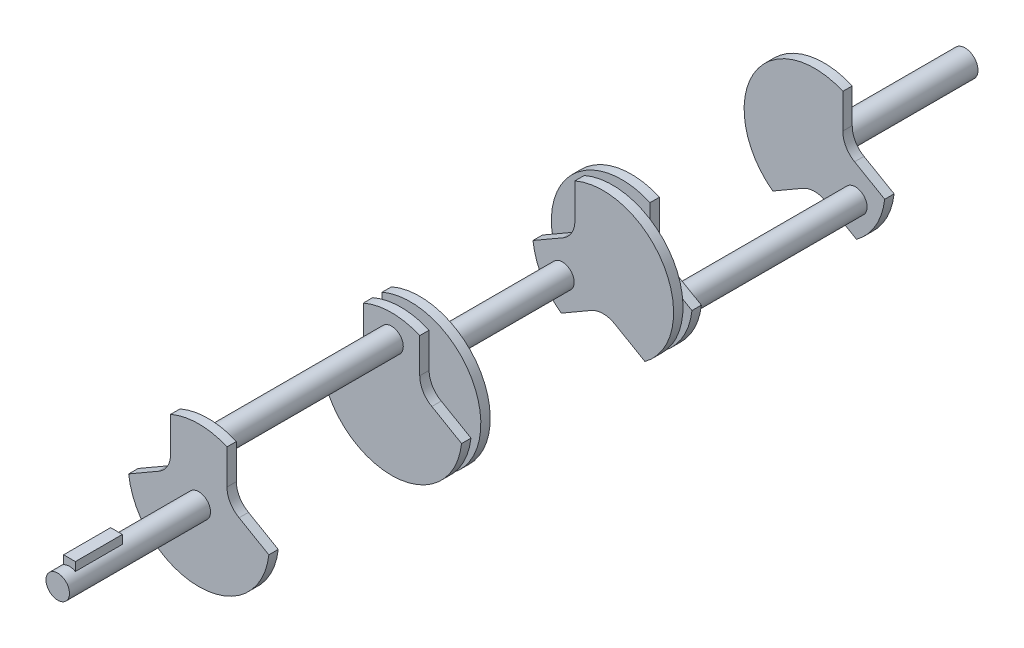
SolidWorks part; units mm, degrees
note: The reader was unsure of these and kept them because the rebuilt part matched: shared geometry of "Sketch3<2>".
ref_plane "Front Plane" through (0, 0, 0) normal (0, 0, 1) x (1, 0, 0)
ref_plane "Top Plane" through (0, 0, 0) normal (0, 1, 0) x (1, 0, 0)
ref_plane "Right Plane" through (0, 0, 0) normal (1, 0, 0) x (0, 0, -1)
sketch "Sketch1" plane through (0, 0, 0) normal (0, 0, 1) x (1, 0, 0)
  line L0 (0, 0) -> (0, 38.1) construction
  line L1 (0, 0) -> (32.9956, -19.05) construction
  line L2 (0, 0) -> (-32.9956, -19.05) construction
  line L3 (15.24, 16.129) -> (15.24, 34.9192)
  line L4 (-15.24, 16.129) -> (-15.24, 34.9192)
  line L5 (21.4019, 5.2413) -> (40.6156, -5.8518)
  line L6 (-21.4019, 5.2413) -> (-37.8609, -4.2614)
  line L7 (-7.62, 13.1982) -> (-40.6156, -5.8518) construction
  line L8 (7.62, 13.1982) -> (40.6156, -5.8518) construction
  line L9 (15.24, 0) -> (15.24, 38.1) construction
  line L10 (-15.24, 0) -> (-15.24, 38.1) construction
  arc A0 (15.24, 34.9192) -> (-15.24, 34.9192) centre (0, 0) ccw
  arc A1 (-37.8609, -4.2614) -> (37.8609, -4.2614) centre (0, 0) ccw
  arc A2 (15.24, 16.129) -> (21.78, 5.023) centre (27.94, 16.129) ccw
  arc A3 (-21.78, 5.023) -> (-15.24, 16.129) centre (-27.94, 16.129) ccw
  dimension "D1" = 76.2
  dimension "D9" = 25.4
  dimension "D11" = 25.4
  dimension "D2" = 120
  dimension "D3" = 120
  dimension "D4" = 15.24
  dimension "D8" = 16.129
  dimension "D10" = 16.129
  dimension "D5" = 15.24
  dimension "D6" = 15.24
  dimension "D7" = 15.24
extrude "Boss-Extrude1" add sketch "Sketch1" against normal blind 5.08 contours L6 A1 L5 L3 A0 L4
pattern_linear "LPattern1" count 2 spacing 104.14 along (0, 0, -1) of bodies 101
sketch "Sketch2" plane through (0, 0, -5.08) normal (0, 0, -1) x (-1, 0, 0)
  line L0 (0, 0) -> (0, 25.4) construction
  circle A0 centre (0, 25.4) radius 6.35
  dimension "D2" = 12.7
  dimension "D1" = 25.4
extrude "Boss-Extrude2" add sketch "Sketch2" along normal up to next
pattern_linear "LPattern2" count 3 spacing 114.3 along (0, 0, -1) of bodies 103
move or copy body "Body-Move/Copy1" bodies to move or copy 104 copy no rotation origin (0, 0, 0) rotation axis (0, 0, 1) rotation angle 120
move or copy body "Body-Move/Copy2" bodies to move or copy 105 copy no rotation origin (0, 0, 0) rotation axis (0, 0, -1) rotation angle 120
sketch "Sketch3" plane through (0, 0, -109.22) normal (0, 0, -1) x (-1, 0, 0)
  circle A0 centre (0, 0) radius 12.7
  dimension "D1" = 25.4
extrude "Boss-Extrude3" add sketch "Sketch3" along normal up to next
extrude "Boss-Extrude4" add sketch "Sketch3<2>" along normal up to next from surface
sketch "Sketch3<2>" plane through (0, 0, -109.22) normal (0, 0, -1) x (-1, 0, 0) same geometry as "Sketch3"
sketch "Sketch4" plane through (0, 0, -337.82) normal (0, 0, -1) x (-1, 0, 0)
  circle A0 centre (0, 0) radius 6.985
  dimension "D1" = 13.97
extrude "Boss-Extrude5" add sketch "Sketch4" along normal blind 76.2
sketch "Sketch5" plane through (0, 0, 0) normal (0, 0, 1) x (1, 0, 0)
  circle A0 centre (0, 0) radius 6.35
  dimension "D1" = 12.7
extrude "Boss-Extrude6" add sketch "Sketch5" along normal blind 76.2
sketch "Sketch6" plane through (0, 0, 0) normal (0, 1, 0) x (1, 0, 0)
  line L0 (0, 0) -> (0, -44.45) construction
  line L1 (3.175, -69.85) -> (-3.175, -69.85)
  line L2 (3.175, -69.85) -> (3.175, -44.45)
  line L3 (3.175, -44.45) -> (-3.175, -44.45)
  line L4 (-3.175, -69.85) -> (-3.175, -44.45)
  dimension "D1" = 44.45
  dimension "D2" = 25.4
  dimension "D3" = 6.35
extrude "Boss-Extrude8" add sketch "Sketch6" along normal up to surface (4.6607 mm away) from offset 10.16
